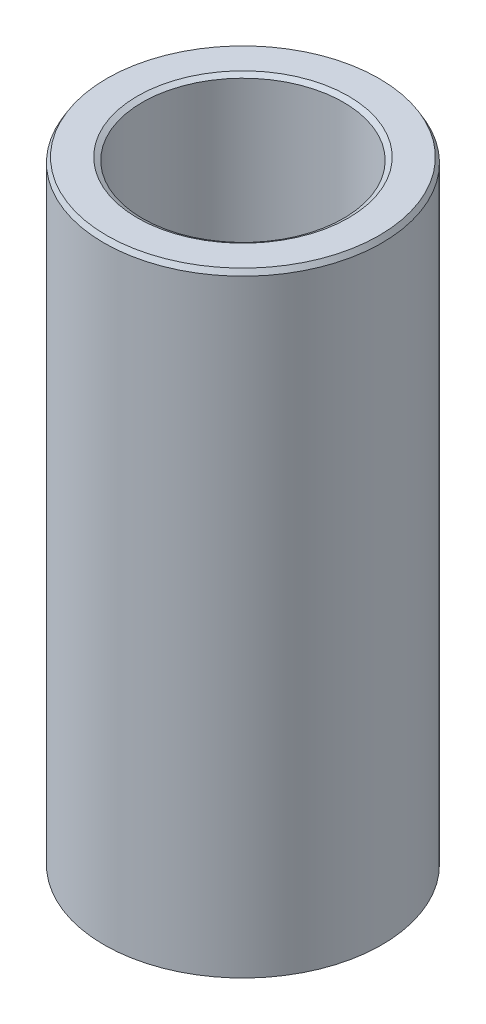
SolidWorks part; units mm, degrees
ref_plane "Front Plane" through (0, 0, 0) normal (0, 0, 1) x (1, 0, 0)
ref_plane "Top Plane" through (0, 0, 0) normal (0, 1, 0) x (1, 0, 0)
ref_plane "Right Plane" through (0, 0, 0) normal (1, 0, 0) x (0, 0, -1)
sketch "Sketch1" plane through (0, 0, 0) normal (0, 1, 0) x (1, 0, 0)
  circle A0 centre (0, 0) radius 27.5
  dimension "SLEEVE_OD" = 55
extrude "Boss-Extrude1" add sketch "Sketch1" along normal blind 121.8302
sketch "Sketch2" plane through (0, 0, 0) normal (0, 1, 0) x (1, 0, 0)
  circle A0 centre (0, 0) radius 19.906
  dimension "BORE_D" = 39.812
extrude "Cut-Extrude1" cut sketch "Sketch2" along normal through all
chamfer "Chamfer1" distance 0.9853 angle 30 4 edges at (0, 121.8302, 19.906) (0, 0, 19.906) (0, 0, 27.5) (0, 121.8302, 27.5) first distance on face at (0, 121.8302, 19.906) first distance on face at (0, 0, 19.906) first distance on face at (0, 121.8302, 27.5)
